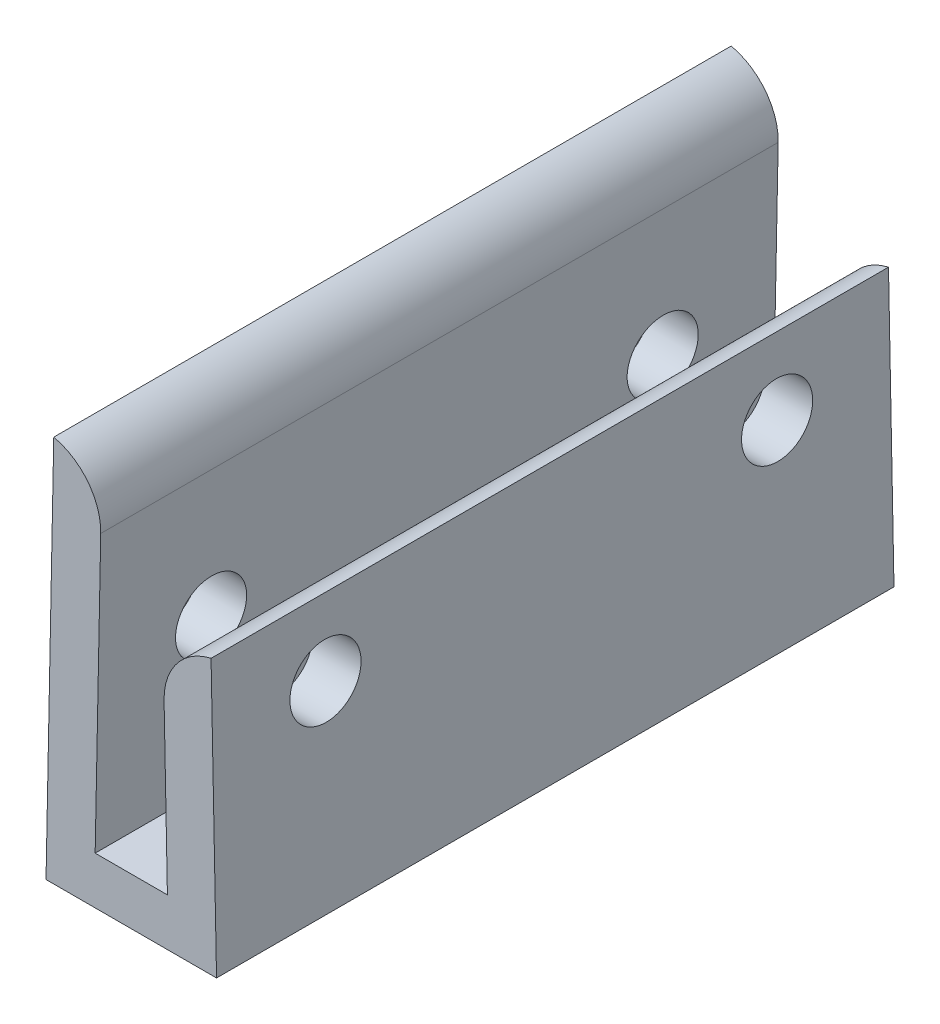
SolidWorks part; units mm, degrees
ref_plane "Front Plane" through (0, 0, 0) normal (0, 0, 1) x (1, 0, 0)
ref_plane "Top Plane" through (0, 0, 0) normal (0, 1, 0) x (1, 0, 0)
ref_plane "Right Plane" through (0, 0, 0) normal (1, 0, 0) x (0, 0, -1)
sketch "Sketch1" plane through (0, 0, 0) normal (0, 0, 1) x (1, 0, 0)
  line L0 (-3.5964, 0) -> (3.5964, 0)
  line L1 (3.5964, 0) -> (3.3651, 11.5637)
  line L2 (3.3651, 11.5637) -> (1.3335, 11.5231)
  line L3 (1.3335, 11.5231) -> (1.524, 2)
  line L4 (1.524, 2) -> (-1.524, 2)
  line L5 (-1.524, 2) -> (-1.3335, 11.5231)
  line L6 (-1.3335, 11.5231) -> (-3.3651, 11.5637)
  line L7 (-3.3651, 11.5637) -> (-3.5964, 0)
  line L8 (-3.3651, 11.5637) -> (-3.2698, 16.3253)
  line L9 (-3.2698, 16.3253) -> (-1.2383, 16.2846)
  line L10 (-1.2383, 16.2846) -> (-1.3335, 11.5231)
  point P11 (0, 0)
  point P13 (0, 2)
  dimension "D1" = 3.048
  dimension "D2" = 2.667
  dimension "D3" = 9.525
  dimension "D4" = 2.032
  dimension "D5" = 2
  dimension "D6" = 4.7625
extrude "Boss-Extrude1" add sketch "Sketch1" along normal blind 28.575 contours L6 L7 L0 L1 L2 L3 L4 L5 | L10 L9 L8 L6 region at (-3.3446, 5.7791, 0) region at (-2.3017, 13.9242, 0)
sketch "Sketch2" plane through (3.595, 0.0719, 0) normal (0.9998, 0.02, 0) x (0, 0, -1)
  line L0 (-23.8125, 8.3191) -> (-4.7625, 8.3191) construction
  line L1 (-28.575, 11.4941) -> (0, 11.4941) construction
  circle A0 centre (-23.8125, 8.3191) radius 1.5
  circle A1 centre (-4.7625, 8.3191) radius 1.5
  point P4 (-14.2875, 8.3191)
  point P7 (-14.2875, 11.4941)
  dimension "D1" = 3
  dimension "D3" = 19.05
  dimension "D2" = 6.35
extrude "Cut-Extrude1" cut sketch "Sketch2" against normal up to next
sketch "Sketch3" plane through (-3.595, 0.0719, 0) normal (-0.9998, 0.02, 0) x (0, 0, 1)
  line L0 (4.7625, 8.2988) -> (23.8125, 8.2988) construction
  line L2 (28.575, -0.0719) -> (0, -0.0719) construction
  circle A0 centre (4.7625, 8.2988) radius 1.5
  circle A1 centre (23.8125, 8.2988) radius 1.5
  point P4 (14.2875, 8.2988)
  point P8 (14.2875, -0.0719)
  dimension "D2" = 3
  dimension "D1" = 19.05
  dimension "D3" = 6.2687
extrude "Cut-Extrude2" cut sketch "Sketch3" against normal up to next
fillet "Fillet1" radius 2.54 2 edges at (1.3335, 11.5231, 14.2875) (-1.2383, 16.2846, 14.2875)
equation "\"bottomThickness\"= .220in"
equation "\"wallThickness\"= .125in"
equation "\"D2@Sketch1\"=\"wallThickness\"-.02in"
equation "\"D1@Sketch1\"=\"wallThickness\"-.005in"
